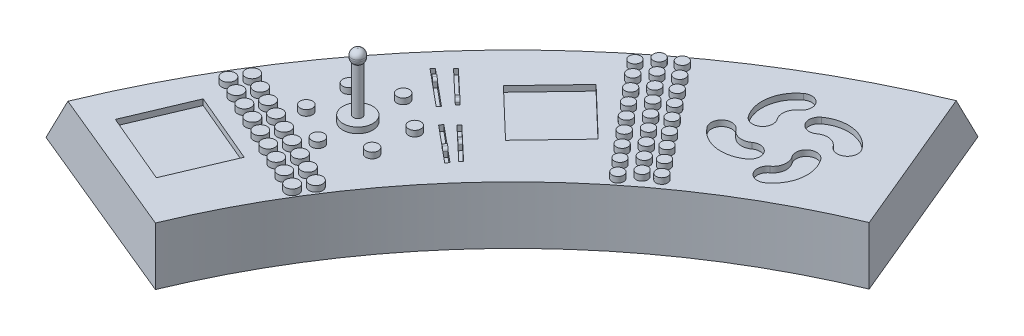
SolidWorks part; units mm, degrees
material "ABS"
ref_plane "Front Plane" through (0, 0, 0) normal (0, 0, 1) x (1, 0, 0)
ref_plane "Top Plane" through (0, 0, 0) normal (0, 1, 0) x (1, 0, 0)
ref_plane "Right Plane" through (0, 0, 0) normal (1, 0, 0) x (0, 0, -1)
sketch "Sketch1" plane through (0, 0, 0) normal (0, 1, 0) x (1, 0, 0)
  line L0 (0, 1495.54) -> (0, -1495.54) construction
  line L1 (0, 0) -> (1057.5065, 1057.5065) construction
  line L2 (1057.5065, 1057.5065) -> (-1057.5065, -1057.5065) construction
  line L3 (-1057.5065, -1057.5065) -> (1057.5065, -1057.5065) construction
  line L4 (1057.5065, -1057.5065) -> (-1057.5065, 1057.5065) construction
  line L5 (-1057.5065, 1057.5065) -> (1057.5065, 1057.5065) construction
  line L6 (440.104, -1057.5065) -> (574.625, -1380.7411)
  line L7 (440.104, 1057.5065) -> (574.625, 1380.7411)
  line L8 (-440.104, 1057.5065) -> (-574.625, 1380.7411)
  line L9 (-440.104, -1057.5065) -> (-574.625, -1380.7411)
  line L10 (-1058.4838, 437.7482) -> (-1382.0172, 571.5491)
  circle A0 centre (0, 0) radius 1495.54
  arc A2 (440.104, 1057.5065) -> (440.104, -1057.5065) centre (0, 0) cw
  arc A3 (-440.104, -1057.5065) -> (-440.104, 1057.5065) centre (0, 0) cw
  arc A4 (-440.104, 1057.5065) -> (-1058.4838, 437.7482) centre (0, 0) ccw
extrude "Boss-Extrude1" add sketch "Sketch1" along normal blind 100 contours L10 A3 L8 A0 region at (-916.326, 0, -914.2879)
chamfer "Chamfer1" distance 100 angle 35 1 edges at (-1058.6832, 100, -1056.3285) first distance on face at (-1018.5021, 50, -1016.2368)
sketch "Sketch2" plane through (0, 100, 0) normal (0, 1, 0) x (1, 0, 0)
  line L0 (-1248.8423, 558.6772) -> (-1125.6399, 506.5387)
  line L1 (-1248.8423, 558.6772) -> (-1203.5398, 665.7263)
  line L2 (-1125.6399, 506.5387) -> (-1080.3374, 613.5878)
  line L3 (-1203.5398, 665.7263) -> (-1080.3374, 613.5878)
extrude "Cut-Extrude1" cut sketch "Sketch2" against normal blind 10
sketch "Sketch3" plane through (0, 100, 0) normal (0, 1, 0) x (1, 0, 0)
  circle A0 centre (-1204.8141, 710.8155) radius 11.5832
  circle A1 centre (-1177.8503, 697.6643) radius 11.5832
  circle A2 centre (-1150.8865, 684.5132) radius 11.5832
  circle A3 centre (-1123.9226, 671.3621) radius 11.5832
  circle A4 centre (-1096.9588, 658.2109) radius 11.5832
  circle A5 centre (-1069.995, 645.0598) radius 11.5832
  circle A6 centre (-1043.0312, 631.9086) radius 11.5832
  circle A7 centre (-1016.0674, 618.7575) radius 11.5832
  circle A8 centre (-989.1035, 605.6064) radius 11.5832
  circle A9 centre (-1162.3991, 723.3793) radius 11.5832
  circle A10 centre (-1135.4353, 710.2282) radius 11.5832
  circle A11 centre (-1108.4715, 697.0771) radius 11.5832
  circle A12 centre (-1081.5077, 683.9259) radius 11.5832
  circle A13 centre (-1054.5439, 670.7748) radius 11.5832
  circle A14 centre (-1027.58, 657.6237) radius 11.5832
  circle A15 centre (-1000.6162, 644.4725) radius 11.5832
  circle A16 centre (-973.6524, 631.3214) radius 11.5832
  circle A17 centre (-1189.363, 736.5305) radius 11.5832
  dimension "D1" = 9
  dimension "D2" = 2
extrude "Boss-Extrude2" add sketch "Sketch3" along normal blind 10
sketch "Sketch4" plane through (0, 100, 0) normal (0, 1, 0) x (1, 0, 0)
  circle A0 centre (-1091.3889, 806.406) radius 10.7258
  circle A1 centre (-1028.8581, 837.8685) radius 10.7258
  circle A2 centre (-970.3453, 799.4465) radius 10.7258
  circle A3 centre (-974.3634, 729.5619) radius 10.7258
  circle A4 centre (-1036.8942, 698.0994) radius 10.7258
  circle A5 centre (-1095.407, 736.5214) radius 10.7258
  dimension "D1" = 6
extrude "Boss-Extrude3" add sketch "Sketch4" along normal blind 10
sketch "Sketch5" plane through (0, 100, 0) normal (0, 1, 0) x (1, 0, 0)
  line L4 (-1052.1599, 907.8326) -> (-989.7445, 856.0222)
  line L5 (-1052.1599, 907.8326) -> (-1047.9864, 912.8604)
  line L6 (-989.7445, 856.0222) -> (-985.571, 861.05)
  line L7 (-1047.9864, 912.8604) -> (-985.571, 861.05)
  line L8 (-960.2346, 830.6981) -> (-897.8192, 778.8877)
  line L9 (-960.2346, 830.6981) -> (-956.061, 835.7259)
  line L10 (-956.061, 835.7259) -> (-893.6456, 783.9155)
  line L11 (-897.8192, 778.8877) -> (-893.6456, 783.9155)
  dimension "D1" = 2
extrude "Cut-Extrude2" cut sketch "Sketch5" against normal blind 10
sketch "Sketch6" plane through (0, 100, 0) normal (0, 1, 0) x (1, 0, 0)
  line L0 (-1032.0136, 928.4032) -> (-975.4146, 874.9307)
  line L1 (-1032.0136, 928.4032) -> (-1027.9251, 932.7307)
  line L2 (-975.4146, 874.9307) -> (-971.3261, 879.2583)
  line L3 (-1027.9251, 932.7307) -> (-971.3261, 879.2583)
  line L4 (-944.2512, 846.5634) -> (-887.6521, 793.0909)
  line L5 (-944.2512, 846.5634) -> (-940.1627, 850.8909)
  line L6 (-940.1627, 850.8909) -> (-883.5637, 797.4185)
  line L7 (-887.6521, 793.0909) -> (-883.5637, 797.4185)
  dimension "D1" = 2
extrude "Cut-Extrude3" cut sketch "Sketch6" against normal blind 10
sketch "Sketch7" plane through (0, 90, 0) normal (0, 1, 0) x (1, 0, 0)
  line L0 (-1038.2772, 897.0031) -> (-1034.4449, 901.6197)
  line L1 (-1038.2772, 897.0031) -> (-1030.7236, 890.7329)
  line L2 (-1034.4449, 901.6197) -> (-1026.8913, 895.3496)
  line L3 (-1030.7236, 890.7329) -> (-1026.8913, 895.3496)
  line L4 (-985.571, 861.05) -> (-1047.9864, 912.8604) construction
  dimension "D1" = 6
extrude "Boss-Extrude5" add sketch "Sketch7" along normal blind 14
fillet "Fillet2" radius 5 1 edges at (-1028.8074, 104, -893.0413)
sketch "Sketch8" plane through (0, 90, 0) normal (0, 1, 0) x (1, 0, 0)
  line L0 (-920.5471, 806.2461) -> (-924.8533, 801.0584)
  line L1 (-920.5471, 806.2461) -> (-913.2442, 800.1841)
  line L2 (-924.8533, 801.0584) -> (-917.5505, 794.9964)
  line L3 (-913.2442, 800.1841) -> (-917.5505, 794.9964)
  line L4 (-893.6456, 783.9155) -> (-956.061, 835.7259) construction
extrude "Boss-Extrude6" add sketch "Sketch8" along normal blind 14
fillet "Fillet3" radius 5 1 edges at (-915.3973, 104, -797.5902)
sketch "Sketch9" plane through (0, 90, 0) normal (0, 1, 0) x (1, 0, 0)
  line L0 (-917.4233, 829.4076) -> (-921.5117, 825.0801)
  line L1 (-917.4233, 829.4076) -> (-910.5466, 822.9109)
  line L2 (-921.5117, 825.0801) -> (-914.6351, 818.5833)
  line L3 (-910.5466, 822.9109) -> (-914.6351, 818.5833)
  line L4 (-883.5637, 797.4185) -> (-940.1627, 850.8909) construction
  line L5 (-944.2512, 846.5634) -> (-887.6521, 793.0909) construction
extrude "Boss-Extrude7" add sketch "Sketch9" along normal blind 14
fillet "Fillet4" radius 5 1 edges at (-912.5909, 104, -820.7471)
sketch "Sketch10" plane through (0, 90, 0) normal (0, 1, 0) x (1, 0, 0)
  line L0 (-982.9956, 890.2831) -> (-987.0841, 885.9556)
  line L1 (-982.9956, 890.2831) -> (-976.2545, 883.9144)
  line L2 (-987.0841, 885.9556) -> (-980.343, 879.5868)
  line L3 (-976.2545, 883.9144) -> (-980.343, 879.5868)
  line L4 (-971.3261, 879.2583) -> (-1027.9251, 932.7307) construction
  line L5 (-1032.0136, 928.4032) -> (-975.4146, 874.9307) construction
extrude "Boss-Extrude8" add sketch "Sketch10" along normal blind 14
fillet "Fillet5" radius 5 1 edges at (-978.2987, 104, -881.7506)
sketch "Sketch11" plane through (0, 100, 0) normal (0, 1, 0) x (1, 0, 0)
  line L0 (-962.9727, 945.8833) -> (-879.042, 865.6407)
  line L1 (-962.9727, 945.8833) -> (-884.4013, 1028.0659)
  line L2 (-879.042, 865.6407) -> (-800.4706, 947.8234)
  line L3 (-884.4013, 1028.0659) -> (-800.4706, 947.8234)
extrude "Cut-Extrude4" cut sketch "Sketch11" against normal blind 10
sketch "Sketch12" plane through (0, 100, 0) normal (0, 1, 0) x (1, 0, 0)
  circle A0 centre (-878.5926, 1089.6189) radius 10
  circle A1 centre (-859.309, 1066.6376) radius 10
  circle A2 centre (-840.0253, 1043.6563) radius 10
  circle A3 centre (-820.7417, 1020.6749) radius 10
  circle A4 centre (-801.4581, 997.6936) radius 10
  circle A5 centre (-782.1745, 974.7123) radius 10
  circle A6 centre (-762.8908, 951.7309) radius 10
  circle A7 centre (-743.6072, 928.7496) radius 10
  circle A8 centre (-724.3236, 905.7683) radius 10
  circle A9 centre (-841.2545, 1090.5967) radius 10
  circle A10 centre (-821.9709, 1067.6153) radius 10
  circle A11 centre (-802.6873, 1044.634) radius 10
  circle A12 centre (-783.4036, 1021.6527) radius 10
  circle A13 centre (-764.12, 998.6713) radius 10
  circle A14 centre (-744.8364, 975.69) radius 10
  circle A15 centre (-725.5527, 952.7087) radius 10
  circle A16 centre (-706.2691, 929.7273) radius 10
  circle A17 centre (-860.5381, 1113.578) radius 10
  dimension "D1" = 9
  dimension "D2" = 2
extrude "Boss-Extrude9" add sketch "Sketch12" along normal blind 10
sketch "Sketch13" plane through (0, 100, 0) normal (0, 1, 0) x (1, 0, 0)
  circle A0 centre (-835.2815, 1128.5572) radius 10
  circle A1 centre (-816.4019, 1105.2429) radius 10
  circle A2 centre (-797.5222, 1081.9285) radius 10
  circle A3 centre (-778.6426, 1058.6141) radius 10
  circle A4 centre (-759.763, 1035.2997) radius 10
  circle A5 centre (-740.8834, 1011.9853) radius 10
  circle A6 centre (-722.0038, 988.671) radius 10
  circle A7 centre (-703.1242, 965.3566) radius 10
  circle A8 centre (-684.2446, 942.0422) radius 10
  dimension "D1" = 9
extrude "Boss-Extrude10" add sketch "Sketch13" along normal blind 10
sketch "Sketch15" plane through (0, 100, 0) normal (0, 1, 0) x (1, 0, 0)
  arc A0 (-680.3009, 1180.1983) -> (-689.4622, 1122.1462) centre (-655.8555, 1146.5917) ccw construction
  arc A1 (-690.8221, 1194.6625) -> (-703.9263, 1111.6251) centre (-655.8555, 1146.5917) ccw
  arc A2 (-669.7798, 1165.7342) -> (-674.9981, 1132.6674) centre (-655.8555, 1146.5917) ccw
  arc A3 (-669.7798, 1165.7342) -> (-690.8221, 1194.6625) centre (-680.3009, 1180.1983) ccw
  arc A4 (-703.9263, 1111.6251) -> (-674.9981, 1132.6674) centre (-689.4622, 1122.1462) ccw
  arc A5 (-571.0392, 1150.8408) -> (-629.0913, 1160.0021) centre (-604.6458, 1126.3954) ccw construction
  arc A6 (-556.575, 1161.362) -> (-639.6124, 1174.4662) centre (-604.6458, 1126.3954) ccw
  arc A7 (-585.5033, 1140.3196) -> (-618.5701, 1145.538) centre (-604.6458, 1126.3954) ccw
  arc A8 (-585.5033, 1140.3196) -> (-556.575, 1161.362) centre (-571.0392, 1150.8408) ccw
  arc A9 (-639.6124, 1174.4662) -> (-618.5701, 1145.538) centre (-629.0913, 1160.0021) ccw
  arc A10 (-600.3967, 1041.579) -> (-591.2354, 1099.6311) centre (-624.8421, 1075.1857) ccw construction
  arc A11 (-589.8755, 1027.1149) -> (-576.7713, 1110.1523) centre (-624.8421, 1075.1857) ccw
  arc A12 (-610.9179, 1056.0432) -> (-605.6996, 1089.11) centre (-624.8421, 1075.1857) ccw
  arc A13 (-610.9179, 1056.0432) -> (-589.8755, 1027.1149) centre (-600.3967, 1041.579) ccw
  arc A14 (-576.7713, 1110.1523) -> (-605.6996, 1089.11) centre (-591.2354, 1099.6311) ccw
  arc A15 (-709.6585, 1070.9366) -> (-651.6064, 1061.7753) centre (-676.0518, 1095.382) ccw construction
  arc A16 (-724.1226, 1060.4154) -> (-641.0852, 1047.3112) centre (-676.0518, 1095.382) ccw
  arc A17 (-695.1944, 1081.4577) -> (-662.1275, 1076.2394) centre (-676.0518, 1095.382) ccw
  arc A18 (-695.1944, 1081.4577) -> (-724.1226, 1060.4154) centre (-709.6585, 1070.9366) ccw
  arc A19 (-641.0852, 1047.3112) -> (-662.1275, 1076.2394) centre (-651.6064, 1061.7753) ccw
  point P3 (-696.9046, 1153.0697)
  point P13 (-598.1679, 1167.4444)
  point P21 (-583.7931, 1068.7077)
  point P29 (-682.5298, 1054.333)
  dimension "D1" = 4
extrude "Cut-Extrude5" cut sketch "Sketch15" against normal blind 10
sketch "Sketch16" plane through (0, 100, 0) normal (0, 1, 0) x (1, 0, 0)
  circle A0 centre (-1035.3341, 765.7253) radius 25.94
extrude "Boss-Extrude11" add sketch "Sketch16" along normal blind 10
ref_point "Point1"
sketch "Sketch18" plane through (0, 110, 0) normal (0, 1, 0) x (1, 0, 0)
  circle A0 centre (-1035.3341, 765.7253) radius 7.8307
extrude "Boss-Extrude12" add sketch "Sketch18" along normal blind 80
ref_point "Point2"
sketch "Sketch20" plane through (0, 190, 0) normal (0, 1, 0) x (1, 0, 0)
  circle A0 centre (-1035.3341, 765.7253) radius 10.8465
extrude "Boss-Extrude13" add sketch "Sketch20" along normal blind 20
fillet "Fillet6" radius 10 1 edges at (-1035.3341, 210, -754.8787)
fillet "Fillet7" radius 10 1 edges at (-1035.3341, 190, -754.8787)
